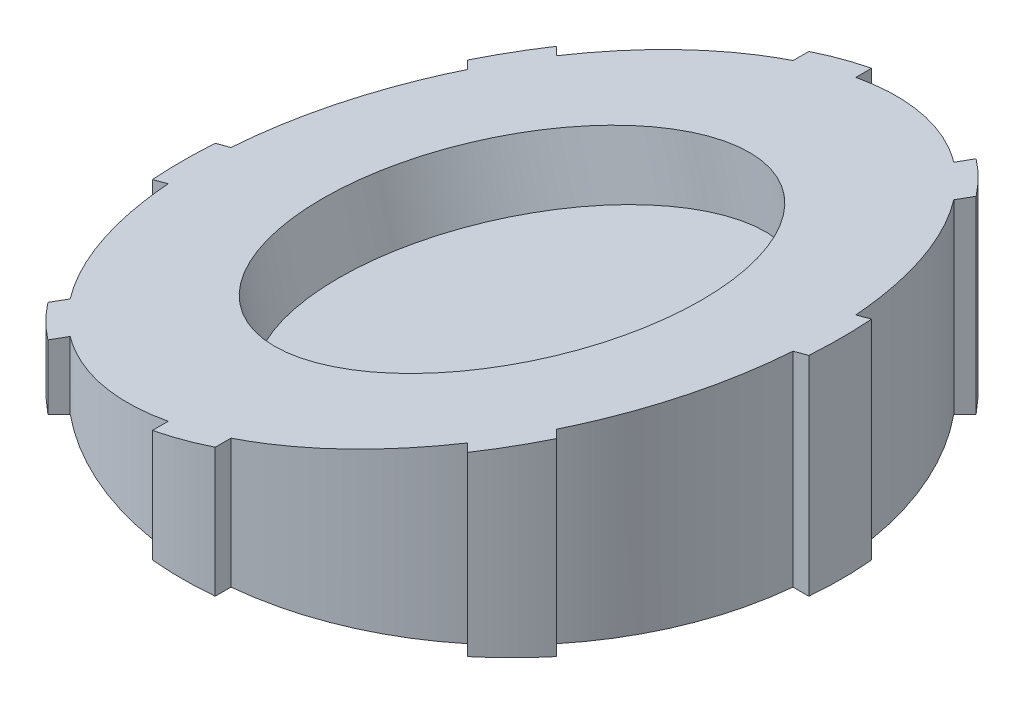
SolidWorks part; units mm, degrees
ref_plane "前视基准面" through (0, 0, 0) normal (0, 0, 1) x (1, 0, 0)
ref_plane "上视基准面" through (0, 0, 0) normal (0, 1, 0) x (1, 0, 0)
ref_plane "右视基准面" through (0, 0, 0) normal (1, 0, 0) x (0, 0, -1)
sketch "草图1" plane through (0, 0, 0) normal (0, 1, 0) x (1, 0, 0)
  circle A0 centre (0, 0) radius 20
  dimension "D1" = 40
extrude "凸台-拉伸1" add sketch "草图1" along normal blind 20
sketch "草图3" plane through (0, 20, 0) normal (0, 1, 0) x (1, 0, 0)
  line L2 (-2, -20.9045) -> (-2, 20.9045)
  line L4 (2, -20.9045) -> (2, 20.9045)
  line L5 (-1.4217, -20.9518) -> (1.4217, 20.9518) construction
  line L6 (-1.4217, 20.9518) -> (1.4217, -20.9518) construction
  arc A0 (2, 20.9045) -> (-2, 20.9045) centre (0, 0) ccw
  arc A1 (-2, -20.9045) -> (2, -20.9045) centre (0, 0) ccw
  dimension "D1" = 42
extrude "凸台-拉伸2" add sketch "草图3" against normal blind 20
pattern_circular "阵列(圆周)1" count 8 over 360 about axis through (0, 20, 0) along (0, -1, 0) of "凸台-拉伸2"
sketch "草图2" plane through (0, 0, 0) normal (0, 0, 1) x (1, 0, 0)
  line L0 (-21.2189, 2) -> (25.6615, 14.5616)
  line L2 (25.6615, 14.5616) -> (25.6615, 41.5119)
  line L3 (25.6615, 41.5119) -> (-21.2189, 43.8579)
  line L4 (-21.2189, 43.8579) -> (-21.2189, 2)
  line L5 (-20, 0) -> (20, 0) construction
  point P2 (-21.8163, 2)
  point P3 (-20.4758, 2)
  point P8 (-20, 2)
  point P9 (-21.2189, 2)
  dimension "D1" = 2
  dimension "D2" = 15
extrude "切除-拉伸1" cut sketch "草图2" against normal mid plane 68
ref_axis "基准轴1" through (0, 0, 0) along (0, -1, 0)
ref_point "点1"
sketch "草图5" plane through (-1.9214, 7.1707, 0) normal (-0.2588, 0.9659, 0) x (0.9659, 0.2588, 0)
  circle A0 centre (1.9892, 0) radius 12.5
  dimension "D1" = 25
extrude "切除-拉伸2" cut sketch "草图5" against normal blind 4
